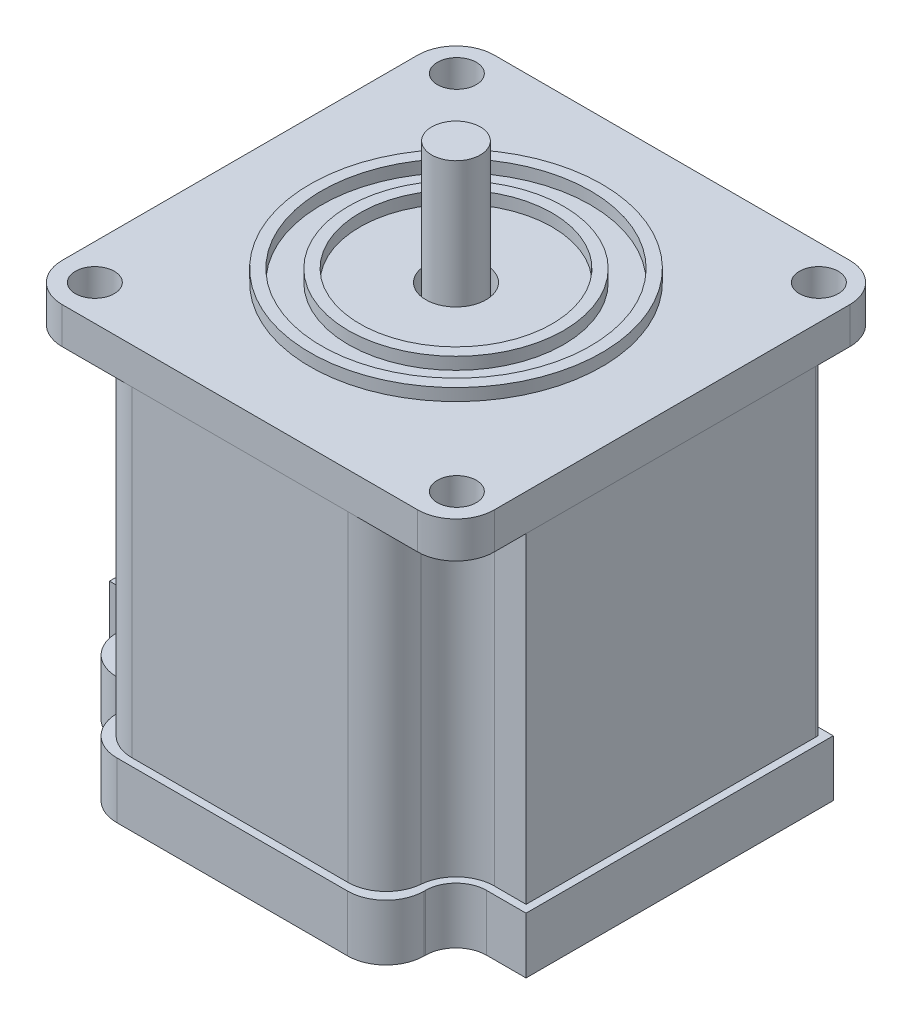
SolidWorks part; units mm, degrees
ref_plane "Front Plane" through (0, 0, 0) normal (0, 0, 1) x (1, 0, 0)
ref_plane "Top Plane" through (0, 0, 0) normal (0, 1, 0) x (1, 0, 0)
ref_plane "Right Plane" through (0, 0, 0) normal (1, 0, 0) x (0, 0, -1)
sketch "Sketch1" plane through (0, 0, 0) normal (0, 1, 0) x (1, 0, 0)
  line L1 (-28.2, -28.2) -> (28.2, -28.2)
  line L2 (-28.2, -28.2) -> (-28.2, 28.2)
  line L3 (-28.2, 28.2) -> (28.2, 28.2)
  line L4 (28.2, -28.2) -> (28.2, 28.2)
  line L5 (-28.2, -28.2) -> (28.2, 28.2) construction
  line L6 (-28.2, 28.2) -> (28.2, -28.2) construction
  point P0 (0, 0)
  dimension "D1" = 56.4
  dimension "D2" = 56.4
extrude "Boss-Extrude1" add sketch "Sketch1" along normal mid plane 54
sketch "Sketch2" plane through (0, 27, 0) normal (0, 1, 0) x (1, 0, 0)
  circle A0 centre (0, 0) radius 19.05
  circle A1 centre (0, 0) radius 17.55
  circle A2 centre (0, 0) radius 14.05
  circle A3 centre (0, 0) radius 12.55
  dimension "D1" = 25.1
  dimension "D2" = 28.1
  dimension "D3" = 35.1
  dimension "D4" = 38.1
extrude "Boss-Extrude2" add sketch "Sketch2" along normal blind 1.59 contours A2 A3 | A0 A1 region at (-18.5112, 27, 0) region at (-13.6526, 27, 0)
sketch "Sketch3" plane through (0, -27, 0) normal (0, -1, 0) x (1, 0, 0)
  line L1 (-28.2, 28.2) -> (-19.06, 28.2)
  line L2 (-28.2, 28.2) -> (-28.2, 19.05)
  line L3 (-28.2, 19.05) -> (-19.06, 19.05)
  line L4 (-19.06, 28.2) -> (-19.06, 19.05)
  line L5 (-23.63, 19.05) -> (-23.63, 28.2) construction
  line L6 (-28.2, 23.625) -> (-19.06, 23.625) construction
  point P212 (-23.63, 23.625)
  dimension "D1" = 9.14
  dimension "D2" = 9.15
extrude "Cut-Extrude1" cut sketch "Sketch3" against normal blind 49.24
pattern_linear "LPattern2" count 2 spacing 47.25 along (1, 0, 0) count 2 spacing 47.25 along (0, 0, -1) of "Cut-Extrude1"
sketch "Sketch5" plane through (0, 27, 0) normal (0, 1, 0) x (1, 0, 0)
  circle A0 centre (-23.57, -23.57) radius 2.54
  dimension "D1" = 5.08
  dimension "D2" = 23.57
  dimension "D3" = 23.57
extrude "Cut-Extrude3" cut sketch "Sketch5" against normal blind 11.24
pattern_linear "LPattern3" count 2 spacing 47.25 along (1, 0, 0) count 2 spacing 47.25 along (0, 0, -1) of "Cut-Extrude3"
sketch "Sketch6" plane through (0, 27, 0) normal (0, 1, 0) x (1, 0, 0)
  circle A0 centre (0, 0) radius 3.175
  dimension "D1" = 6.35
extrude "Boss-Extrude3" add sketch "Sketch6" along normal blind 16
sketch "Sketch8" plane through (0, 27, 0) normal (0, 1, 0) x (1, 0, 0)
  circle A0 centre (0, 0) radius 3.925
  circle A1 centre (0, 0) radius 3.175
  dimension "D1" = 7.85
extrude "Cut-Extrude4" cut sketch "Sketch8" against normal blind 8
fillet "Fillet2" radius 5 4 edges at (-19.06, -2.38, 19.05) (-19.06, -2.38, -19.05) (19.05, -2.38, -19.05) (19.05, -2.38, 19.05)
sketch "Sketch9" plane through (-28.2, 0, 0) normal (-1, 0, 0) x (0, 0, 1)
  line L0 (-19.05, -27) -> (19.05, -27) construction
  line L1 (-9.7, -27) -> (9.7, -27)
  line L2 (-9.7, -27) -> (-9.7, -19.67)
  line L3 (-9.7, -19.67) -> (9.7, -19.67)
  line L4 (9.7, -27) -> (9.7, -19.67)
  line L5 (0, -19.67) -> (0, -27) construction
  line L6 (-9.7, -23.335) -> (9.7, -23.335) construction
  point P144 (0, -23.335)
  dimension "D1" = 19.4
  dimension "D2" = 9.7
  dimension "D3" = 7.33
extrude "Boss-Extrude5" add sketch "Sketch9" along normal blind 7.33
sketch "Sketch17" plane through (28.2, 0, 0) normal (1, 0, 0) x (0, 0, -1)
  line L1 (-28.2, -27) -> (-19.06, -27)
  line L2 (-28.2, -27) -> (-28.2, 22.24)
  line L3 (-28.2, 22.24) -> (-19.06, 22.24)
  line L4 (-19.06, -27) -> (-19.06, 22.24)
  line L5 (-23.63, 22.24) -> (-23.63, -27) construction
  line L6 (-28.2, -2.38) -> (-19.06, -2.38) construction
  line L7 (28.2, -27) -> (19.06, -27)
  line L8 (28.2, -27) -> (28.2, 22.24)
  line L9 (28.2, 22.24) -> (19.06, 22.24)
  line L10 (19.06, -27) -> (19.06, 22.24)
  line L11 (23.63, 22.24) -> (23.63, -27) construction
  line L12 (28.2, -2.38) -> (19.06, -2.38) construction
  point P132 (-23.63, -2.38)
  point P178 (23.63, -2.38)
  dimension "D1" = 49.24
  dimension "D2" = 49.24
  dimension "D3" = 9.14
  dimension "D4" = 9.14
extrude "Cut-Extrude7" cut sketch "Sketch17" against normal blind 1
sketch "Sketch19" plane through (0, -27, 0) normal (0, -1, 0) x (1, 0, 0)
  line L0 (-28.2, 19.05) -> (-24.06, 19.05) construction
  line L1 (-28.2, 9.7) -> (-28.2, 19.05) construction
  line L2 (-28.2, -19.05) -> (-28.2, -9.7) construction
  line L3 (-24.06, -19.05) -> (-28.2, -19.05) construction
  line L4 (-19.06, -28.2) -> (-19.06, -24.05) construction
  line L5 (19.05, -28.2) -> (-19.06, -28.2) construction
  line L6 (19.05, -24.05) -> (19.05, -28.2) construction
  line L7 (28.19, -19.05) -> (24.05, -19.05) construction
  line L8 (28.2, 19.06) -> (28.2, -19.06) construction
  line L9 (24.05, 19.05) -> (28.19, 19.05) construction
  line L10 (19.05, 28.2) -> (19.05, 24.05) construction
  line L11 (-19.06, 28.2) -> (19.05, 28.2) construction
  line L12 (-19.06, 24.05) -> (-19.06, 28.2) construction
  line L13 (-28.2, 19.05) -> (-24.06, 19.05)
  line L14 (-28.2, 9.7) -> (-28.2, 19.05)
  line L15 (-28.2, -19.05) -> (-28.2, -9.7)
  line L16 (-24.06, -19.05) -> (-28.2, -19.05)
  line L17 (-19.06, -28.2) -> (-19.06, -24.05)
  line L18 (19.05, -28.2) -> (-19.06, -28.2)
  line L19 (19.05, -24.05) -> (19.05, -28.2)
  line L20 (28.19, -19.05) -> (24.05, -19.05)
  line L21 (28.2, 19.06) -> (28.2, -19.06)
  line L22 (24.05, 19.05) -> (28.19, 19.05)
  line L23 (19.05, 28.2) -> (19.05, 24.05)
  line L24 (-19.06, 28.2) -> (19.05, 28.2)
  line L25 (-19.06, 24.05) -> (-19.06, 28.2)
  line L26 (-28.2, 9.7) -> (-28.2, -9.7)
  line L27 (28.19, 19.05) -> (28.19, -19.05)
  line L28 (-29.2, 9.7) -> (-29.2, -9.7)
  line L29 (-29.2, -20.05) -> (-29.2, -9.7)
  line L30 (-24.06, -20.05) -> (-29.2, -20.05)
  line L31 (-20.06, -29.2) -> (-20.06, -24.05)
  line L32 (20.05, -29.2) -> (-20.06, -29.2)
  line L33 (20.05, -24.05) -> (20.05, -29.2)
  line L34 (29.19, -20.05) -> (24.05, -20.05)
  line L35 (29.19, 20.05) -> (29.19, -20.05)
  line L36 (24.05, 20.05) -> (29.19, 20.05)
  line L37 (20.05, 29.2) -> (20.05, 24.05)
  line L38 (-20.06, 29.2) -> (20.05, 29.2)
  line L39 (-20.06, 24.05) -> (-20.06, 29.2)
  line L40 (-29.2, 20.05) -> (-24.06, 20.05)
  line L41 (-29.2, 9.7) -> (-29.2, 20.05)
  arc A0 (-19.06, -24.05) -> (-24.06, -19.05) centre (-24.06, -24.05) ccw construction
  arc A1 (24.05, -19.05) -> (19.05, -24.05) centre (24.05, -24.05) ccw construction
  arc A2 (19.05, 24.05) -> (24.05, 19.05) centre (24.05, 24.05) ccw construction
  arc A3 (-24.06, 19.05) -> (-19.06, 24.05) centre (-24.06, 24.05) ccw construction
  arc A4 (-19.06, -24.05) -> (-24.06, -19.05) centre (-24.06, -24.05) ccw
  arc A5 (24.05, -19.05) -> (19.05, -24.05) centre (24.05, -24.05) ccw
  arc A6 (19.05, 24.05) -> (24.05, 19.05) centre (24.05, 24.05) ccw
  arc A7 (-24.06, 19.05) -> (-19.06, 24.05) centre (-24.06, 24.05) ccw
  arc A8 (-20.06, -24.05) -> (-24.06, -20.05) centre (-24.06, -24.05) ccw
  arc A9 (24.05, -20.05) -> (20.05, -24.05) centre (24.05, -24.05) ccw
  arc A10 (20.05, 24.05) -> (24.05, 20.05) centre (24.05, 24.05) ccw
  arc A11 (-24.06, 20.05) -> (-20.06, 24.05) centre (-24.06, 24.05) ccw
  line M4 (28.2, 19.06) -> (28.19, 19.06)
  line M5 (28.19, 19.06) -> (28.19, 19.05)
  line M6 (28.19, 19.05) -> (24.05, 19.05)
  arc M7 (24.05, 19.05) -> (19.05, 24.05) centre (24.05, 24.05) cw
  line M8 (19.05, 24.05) -> (19.05, 28.2)
  line M9 (19.05, 28.2) -> (-19.06, 28.2)
  line M10 (-19.06, 28.2) -> (-19.06, 24.05)
  arc M11 (-19.06, 24.05) -> (-24.06, 19.05) centre (-24.06, 24.05) cw
  line M12 (-24.06, 19.05) -> (-28.2, 19.05)
  line M13 (-28.2, 19.05) -> (-28.2, 9.7)
  line M14 (-28.2, 9.7) -> (-35.53, 9.7)
  line M16 (-35.53, -9.7) -> (-28.2, -9.7)
  line M17 (-28.2, -9.7) -> (-28.2, -19.05)
  line M18 (-28.2, -19.05) -> (-24.06, -19.05)
  arc M19 (-24.06, -19.05) -> (-19.06, -24.05) centre (-24.06, -24.05) cw
  line M20 (-19.06, -24.05) -> (-19.06, -28.2)
  line M21 (-19.06, -28.2) -> (19.05, -28.2)
  line M22 (19.05, -28.2) -> (19.05, -24.05)
  arc M23 (19.05, -24.05) -> (24.05, -19.05) centre (24.05, -24.05) cw
  line M24 (24.05, -19.05) -> (28.19, -19.05)
  line M25 (28.19, -19.05) -> (28.19, -19.06)
  line M26 (28.19, -19.06) -> (28.2, -19.06)
  line M27 (28.2, -19.06) -> (28.2, 19.06)
  dimension "D1" = 1
extrude "Boss-Extrude6" add sketch "Sketch19" against normal up to vertex (7.33 mm away) contours A11 L40 L41 L29 L30 A8 L31 L32 L33 A9 L34 L35 L36 A10 L37 L38 L39 M14 M13 M12 M11 M10 M9 M8 M7 M6 M5 M4 M27 M26 M25 M24 M23 M22 M21 M20 M19 M18 M17 M16 | L28 L26 M14 M16 region at (-29.0258, -27, 14.375) region at (-28.7, -27, 0) up to point (-35.53, -19.67, 9.7)
fillet "Fillet3" radius 5 4 edges at (-28.2, 24.62, -28.2) (-28.2, 24.62, 28.2) (28.2, 24.62, -28.2) (28.2, 24.62, 28.2)
sketch "Sketch21" plane through (0, 0, 28.2) normal (0, 0, 1) x (1, 0, 0)
  line L0 (-45.4774, 22.24) -> (41.3312, 22.24)
fillet "Fillet4" radius 5 4 edges at (28.19, 1.285, 19.06) (19.05, 1.285, 28.2) (-19.06, 1.285, 28.2) (-28.2, 1.285, 19.05)
fillet "Fillet5" radius 5 1 edges at (19.05, 1.285, -28.2)
fillet "Fillet6" radius 5 1 edges at (28.2, 1.285, -19.06)
fillet "Fillet7" radius 5 1 edges at (-28.2, 1.285, -19.05)
fillet "Fillet8" radius 5 1 edges at (-19.06, 1.285, -28.2)
fillet "Fillet10" radius 5 1 edges at (-20.06, -23.335, 29.2)
fillet "Fillet11" radius 5 1 edges at (-29.2, -23.335, 20.05)
fillet "Fillet12" radius 5 1 edges at (-29.2, -23.335, -20.05)
fillet "Fillet13" radius 5 1 edges at (-20.06, -23.335, -29.2)
fillet "Fillet14" radius 5 1 edges at (20.05, -23.335, -29.2)
fillet "Fillet15" radius 5 1 edges at (20.05, -23.335, 29.2)
split line "Split Line1"
